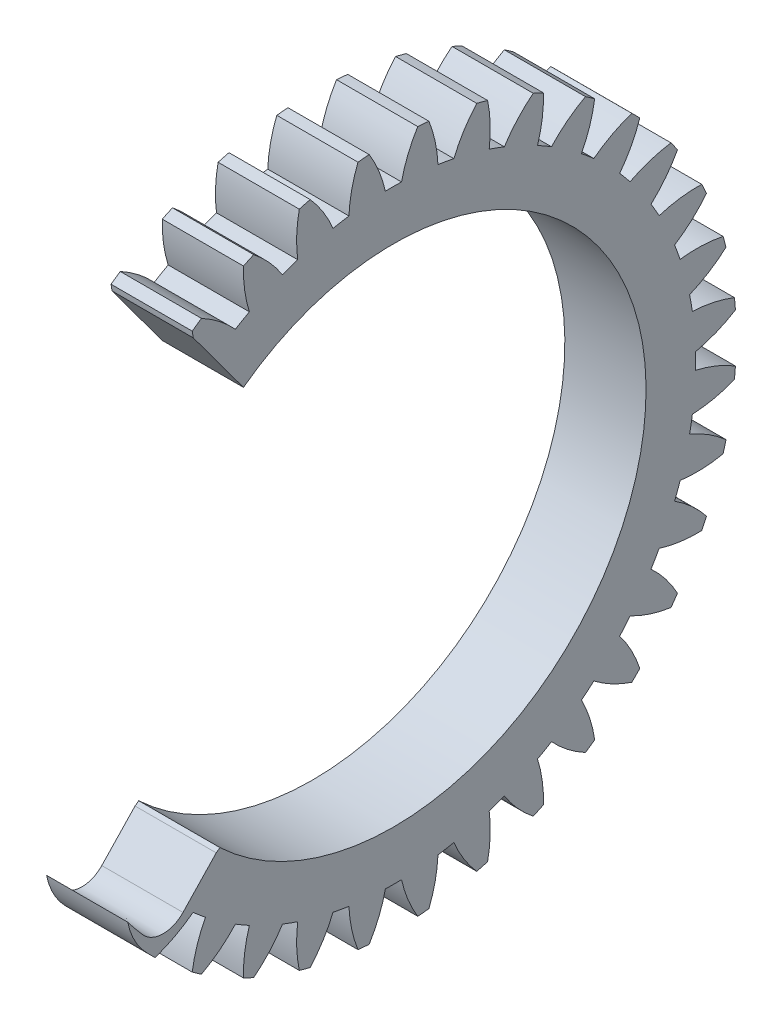
SolidWorks part; units mm, degrees
ref_plane "Plane1" through (0, 0, 0) normal (0, 0, 1) x (1, 0, 0)
ref_plane "Plane2" through (0, 0, 0) normal (0, 1, 0) x (1, 0, 0)
ref_plane "Plane3" through (0, 0, 0) normal (1, 0, 0) x (0, 0, -1)
sketch "HoldingSke" plane through (0, 0, 0) normal (0, 1, 0) x (1, 0, 0)
  line L0 (0, 0) -> (0.4045, -0.2939)
  line L1 (-15, 0) -> (100, 0) construction
  line L2 (0, 0) -> (-2.1039, 2.3779)
  line L3 (0, 0) -> (-11.863, 4.5341)
  line L4 (0, 0) -> (6.9867, 5.0761)
  line L5 (0, 0) -> (-46.8476, -17.4728)
  line L6 (0, 0) -> (-7.4607, -5.0337)
  line L7 (-2.1039, 2.3779) -> (8.6586, 51.2059)
  line L8 (-76.2, 54.61) -> (-71.9, 54.61)
  line L9 (-71.009, 38.7566) -> (-53.1078, 45.2721)
  line L10 (-76.2, 71.12) -> (104.1128, 71.12)
  line L11 (0, 0) -> (-9, 0)
  line L12 (-76.2, 101.6) -> (-76.133, 101.6)
  line L13 (24.9733, 27.94) -> (52.9518, 28.4284)
  line L14 (24.9733, 27.94) -> (24.9743, 27.94)
  line L15 (24.9733, 27.94) -> (100.4006, 29.5858)
  line L16 (-63.627, -2) -> (-12.827, -2)
  circle A0 centre (0, 0) radius 28
  circle A1 centre (0, 0) radius 33.499
  circle A2 centre (0, 0) radius 37.5
  circle A3 centre (0, 0) radius 28
  dimension "Num_teeth" = 36
  dimension "Pitch_radius" = 180.3128
  dimension "Width" = 9
  dimension "Thickness" = 9
sketch "BasProSke" plane through (0, 0, 0) normal (0, 1, 0) x (1, 0, 0)
  line L0 (-10, 0) -> (60, 0) construction
  line L1 (0, 0) -> (0, 38)
  line L2 (0, 0) -> (9, 0)
  line L3 (9, 0) -> (9, 38)
  line L4 (9, 38) -> (0, 38)
  dimension "Thickness" = 9
  dimension "Diameter" = 76
revolve "Base-Revolve" add sketch "BasProSke" angle 360 about L0
sketch "TooCutSke" plane through (0, 0, 0) normal (1, 0, 0) x (0, 0, -1)
  line L1 (0, 0) -> (0, 107) construction
  line L2 (0, 0) -> (-1.6875, 35.9604) construction
  line L3 (0, 0) -> (-6.2701, 71.6676) construction
  line L4 (-1.6875, 35.9604) -> (-3.135, 35.8338) construction
  arc A0 (0.8949, 33.487) -> (-0.8949, 33.487) centre (0, 0) ccw
  arc A1 (2.7061, 37.929) -> (-2.7061, 37.929) centre (0, 0) ccw
  circle A2 centre (0, 0) radius 36 construction
  circle A3 centre (0, 0) radius 33.8289 construction
  arc A4 (-0.8949, 33.487) -> (-2.7061, 37.929) centre (-14.9484, 30.347) ccw
  arc A5 (2.7061, 37.929) -> (0.8949, 33.487) centre (14.9484, 30.347) ccw
extrude "ToothCut" cut sketch "TooCutSke" along normal through all
fillet "Breaks" [suppressed] radius 0.04 tangent propagation no
fillet "RootFillets" [suppressed] radius 0.501
pattern_circular "TeethCuts" count 36 every 10 about axis through (-10, 0, 0) along (1, 0, 0) of "ToothCut", "RootFillets", "Breaks"
sketch "HubNeaOneSke" plane through (0, 0, 0) normal (-1, 0, 0) x (0, 0, 1)
  circle A0 centre (0, 0) radius 33.499
  dimension "Diameter" = 66.998
extrude "HubNearOne" [suppressed] add sketch "HubNeaOneSke" along normal blind 41.0001
sketch "HubNeaBotSke" plane through (0, 0, 0) normal (-1, 0, 0) x (0, 0, 1)
  circle A0 centre (0, 0) radius 33.499
  dimension "Diameter" = 66.998
extrude "HubNearBoth" [suppressed] add sketch "HubNeaBotSke" along normal blind 20.5
ref_plane "FarPln" through (9, 0, 0) normal (1, 0, 0) x (0, 0, -1)
sketch "HubFarSke" plane through (9, 0, 0) normal (1, 0, 0) x (0, 0, -1)
  circle A0 centre (0, 0) radius 33.499
  dimension "Diameter" = 66.998
extrude "HubFar" [suppressed] add sketch "HubFarSke" along normal blind 20.5
sketch "BorSke" plane through (0, 0, 0) normal (1, 0, 0) x (0, 0, -1)
  circle A0 centre (0, 0) radius 28
  dimension "Diameter" = 56
extrude "Bore" cut sketch "BorSke" along normal mid plane 100.0001
sketch "KeySke" plane through (0, 0, 0) normal (1, 0, 0) x (0, 0, -1)
  line L0 (-8, 0) -> (-8, 32.3)
  line L1 (-8, 32.3) -> (8, 32.3)
  line L2 (8, 32.3) -> (8, 0)
  line L3 (0, 0) -> (0, 34) construction
  line L4 (-8, 0) -> (8, 0)
  dimension "Width" = 16
extrude "Keyway" [suppressed] cut sketch "KeySke" along normal mid plane 100.0001
pattern_circular "Keyway2" [suppressed] count 2 every 90 about axis through (-10, 0, 0) along (1, 0, 0) reverse direction yes
sketch "Szkic1" plane through (0, 0, 0) normal (1, 0, 0) x (0, 0, -1)
  line L0 (0, 0) -> (-27.328, 37.0259)
  line L1 (-27.328, 37.0259) -> (-47.6164, -10.233)
  line L2 (-47.6164, -10.233) -> (0, 0)
extrude "Wytnij-wyciągnięcie1" cut sketch "Szkic1" along normal through all
sketch "Szkic2" plane through (0, 0, 0) normal (1, 0, 0) x (0, 0, -1)
  line L0 (-19.6433, -20.6493) -> (-23.3286, -24.5233) construction
  line L1 (-19.6433, -20.6493) -> (-23.3286, -24.5233)
  line L2 (-24.5118, 27.7159) -> (-14.2182, -16.6493)
  line L3 (-14.2182, -16.6493) -> (-19.6433, -20.6493)
  line L4 (-24.5118, 27.7159) -> (-50.9594, 25.255)
  line L5 (-50.9594, 25.255) -> (-37.7356, -29.3697)
  line L6 (-37.7356, -29.3697) -> (-27.7664, -24.4546)
  line L7 (-26.426, -27.3069) -> (-27.3069, -26.426)
  line L8 (-26.426, -27.3069) -> (-25.0675, -25.4318)
  arc A0 (-24.5118, 27.7159) -> (-27.7664, -24.4546) centre (0, 0) ccw construction
  arc A1 (-24.5118, 27.7159) -> (-27.7664, -24.4546) centre (0, 0) ccw
  arc A2 (-27.3069, -26.426) -> (-29.4473, -22.4022) centre (-21.7924, -20.9115) cw
  spline S0 degree 3 poles (273874.4752, 339512.8811) (7601.5471, 9915.3257) (-154.6056, 69.8177) (-27.1426, -24.9996) (-26.9606, -25.1074) (-26.5829, -25.2806) (-26.3868, -25.3469) (-25.9801, -25.4387) (-25.7711, -25.4633) (-25.3572, -25.469) (-25.1483, -25.4503) (-24.7384, -25.37) (-24.5404, -25.3094) (-24.158, -25.1482) (-23.9725, -25.0463) (116.7418, 72.2858) (-8418.6296, 11508.4077) (-264794.1332, 346856.9186) knots -95.625864 -95.625864 -95.625864 -95.625864 0.125 0.125 0.25 0.25 0.375 0.375 0.5 0.5 0.625 0.625 0.75 0.75 0.875 0.875 103.797727 103.797727 103.797727 103.797727 only from (-27.7664, -24.4546) to (-23.3286, -24.5233) construction
  spline S1 degree 3 poles (-27.7664, -24.4546) (-27.6277, -24.6121) (-27.4749, -24.7523) (-27.1426, -24.9996) (-26.9606, -25.1074) (-26.5829, -25.2806) (-26.3868, -25.3469) (-25.9801, -25.4387) (-25.7711, -25.4633) (-25.3572, -25.469) (-25.1483, -25.4503) (-24.7384, -25.37) (-24.5404, -25.3094) (-24.158, -25.1482) (-23.9725, -25.0463) (-23.6312, -24.8102) (-23.4733, -24.6754) (-23.3286, -24.5233) knots 0 0 0 0 0.125 0.125 0.25 0.25 0.375 0.375 0.5 0.5 0.625 0.625 0.75 0.75 0.875 0.875 1 1 1 1
extrude "Wytnij-wyciągnięcie2" cut sketch "Szkic2" against normal blind 43 and the other way through all contours A1 L4 L5 L6 | A1 S1 L1 L3 L2 region at (0, -1.5762, 26.5296) region at (0, 4.8425, 39.1923)
extrude "Dodanie-wyciągnięcie1" add sketch "Szkic2<3>" along normal up to surface (9 mm away) contours A2 L6 A1 | S1 L6 A2 L7 L8 region at (0, -25.7946, 26.8655) region at (0, -23.8723, 28.649) up to face at (9, -1.2954, -9.9994)
sketch "Szkic2<3>" plane through (0, 0, 0) normal (1, 0, 0) x (0, 0, -1) same geometry as "Szkic2"
equation "' \"Module@HoldingSke\" = 6.35"
equation "' \"Num_teeth@HoldingSke\" = 12"
equation "' \"Ap@HoldingSke\" =  20"
equation "' \"Ap@HoldingSke\" = 20"
equation "' \"Width@HoldingSke\" = 0.5 * 25.4"
equation "' \"Hub_dia@HoldingSke\"= 1 * 25.4"
equation "' \"Hub_dia@HoldingSke\" = 1 * 25.4"
equation "' \"Overall_len@HoldingSke\" = 1.0 * 25.4"
equation "' \"Bore@HoldingSke\" = 0.75 * 25.4"
equation "' \"T_dim@HoldingSke\" = 0.1 * 25.4"
equation "' \"Width@KeySke\" = 0.25 * 25.4"
equation "' \"Show_teeth@HoldingSke\" = 13"
equation "' \"Backlash@HoldingSke\" = 0.009 * 25.4"
equation "' \"Addendum_fac@HoldingSke\" = 1.0"
equation "' \"Dedendum_fac@HoldingSke\" = 1.25"
equation "' \"Dedendum_add@HoldingSke\" = 0.00005 * 25.4"
equation "' \"Clearance_fac@HoldingSke\" = 0.25"
equation "\"Pitch@HoldingSke\" = 1 / \"Module@HoldingSke\""
equation "\"Overcut_dia@TooCutSke\" = (\"Num_teeth@HoldingSke\" + 2 * \"Addendum_fac@HoldingSke\") / \"Pitch@HoldingSke\" + 0.002 * 25.4"
equation "\"Pitch_dia@TooCutSke\" = \"Num_teeth@HoldingSke\" / \"Pitch@HoldingSke\""
equation "\"Base_dia@TooCutSke\" = \"Num_teeth@HoldingSke\" / \"Pitch@HoldingSke\" * cos((\"Ap@HoldingSke\"  * 3.14159265 / 180))"
equation "\"Root_dia@TooCutSke\" = (\"Num_teeth@HoldingSke\" + 2) / \"Pitch@HoldingSke\" - 2 * (\"Addendum_fac@HoldingSke\" + \"Dedendum_fac@HoldingSke\") / \"Pitch@HoldingSke\" - \"Dedendum_add@HoldingSke\" * 2"
equation "\"Half_ang@TooCutSke\" = 180 / \"Num_teeth@HoldingSke\""
equation "\"Half_CT@TooCutSke\" = \"Num_teeth@HoldingSke\" / \"Pitch@HoldingSke\" * sin((3.14159265 / 2 / \"Num_teeth@HoldingSke\")) / 2 - 7 * \"Backlash@HoldingSke\" / 4"
equation "\"Flank_rad@TooCutSke\" = \"Num_teeth@HoldingSke\" / \"Pitch@HoldingSke\" / 5"
equation "\"Radius@RootFillets\" = \"Clearance_fac@HoldingSke\" / \"Pitch@HoldingSke\" + \"Dedendum_add@HoldingSke\""
equation "\"Break_rad@Breaks\" = 0.02 / \"Pitch@HoldingSke\""
equation "\"Thickness@HoldingSke\" = \"Width@HoldingSke\""
equation "\"OAL@HoldingSke\" = \"Thickness@HoldingSke\""
equation "\"MHD@HoldingSke\" = (\"Num_teeth@HoldingSke\" + 2) / \"Pitch@HoldingSke\" - 2 * (\"Addendum_fac@HoldingSke\" + \"Dedendum_fac@HoldingSke\")  / \"Pitch@HoldingSke\" - \"Dedendum_add@HoldingSke\" * 2"
equation "\"MBD@HoldingSke\" = (\"Num_teeth@HoldingSke\" + 2) / \"Pitch@HoldingSke\" - 2 * (\"Addendum_fac@HoldingSke\" + \"Dedendum_fac@HoldingSke\")  / \"Pitch@HoldingSke\" - \"Dedendum_add@HoldingSke\" * 2 - 0.002 * 25.4"
equation "\"MHD@HoldingSke\" = ((sgn( \"MHD@HoldingSke\" - \"Hub_dia@HoldingSke\" )-1)*( \"MHD@HoldingSke\" - \"Hub_dia@HoldingSke\" ))/-2+ \"Hub_dia@HoldingSke\""
equation "\"MBD@HoldingSke\" = ((sgn( \"MBD@HoldingSke\" - \"Bore@HoldingSke\" )-1)*( \"MBD@HoldingSke\" - \"Bore@HoldingSke\" ))/-2+ \"Bore@HoldingSke\""
equation "\"OAL@HoldingSke\" = ((sgn( \"OAL@HoldingSke\" - \"Overall_len@HoldingSke\" )+1)*( \"OAL@HoldingSke\" - \"Overall_len@HoldingSke\" ))/2 + \"Overall_len@HoldingSke\" + 0.000002 * 25.4"
equation "\"Num_teeth@TeethCuts\" = int( \"Show_teeth@HoldingSke\" ) + 1"
equation "\"Num_teeth@TeethCuts\" = ((sgn( \"Num_teeth@TeethCuts\" - \"Num_teeth@HoldingSke\" )-1)*( \"Num_teeth@TeethCuts\" - \"Num_teeth@HoldingSke\" ))/-2+ \"Num_teeth@HoldingSke\""
equation "\"Num_teeth@TeethCuts\" = ((sgn( \"Num_teeth@TeethCuts\" - 2.0)+1)*( \"Num_teeth@TeethCuts\" - 2.0))/2 +2.0"
equation "\"Angle@TeethCuts\" = 360.0 / \"Num_teeth@HoldingSke\""
equation "\"Diameter@BasProSke\" = (\"Num_teeth@HoldingSke\" + 2 * \"Addendum_fac@HoldingSke\") / \"Pitch@HoldingSke\""
equation "\"Thickness@BasProSke\"  = \"Thickness@HoldingSke\""
equation "' \"Fillet_rad@BasProSke\" =  \"Thickness@HoldingSke\" * 0.05"
equation "' \"Fillet_rad@BasProSke\" = \"Thickness@HoldingSke\" * 0.05"
equation "\"MHD@HoldingSke\" = ((sgn( \"MHD@HoldingSke\" - \"Root_dia@TooCutSke\" )-1)*( \"MHD@HoldingSke\" - \"Root_dia@TooCutSke\" ))/-2+ \"Root_dia@TooCutSke\""
equation "\"Diameter@HubNeaOneSke\" = \"MHD@HoldingSke\""
equation "\"Length@HubNearOne\" = \"OAL@HoldingSke\" - \"Thickness@BasProSke\""
equation "\"Diameter@HubNeaBotSke\" = \"MHD@HoldingSke\""
equation "\"Length@HubNearBoth\" = ( \"OAL@HoldingSke\" - \"Thickness@BasProSke\" ) / 2.0"
equation "\"Thickness@FarPln\" = \"Thickness@BasProSke\""
equation "\"Diameter@HubFarSke\" = \"MHD@HoldingSke\""
equation "\"Length@HubFar\" = ( \"OAL@HoldingSke\" - \"Thickness@BasProSke\" ) / 2.0"
equation "\"Diameter@BorSke\" = \"MBD@HoldingSke\""
equation "\"D1@Bore\" = \"OAL@HoldingSke\" * 2.0"
equation "\"D1@Keyway\" = \"OAL@HoldingSke\" * 2.0"
equation "\"Offset@KeySke\" = \"T_dim@HoldingSke\" + \"MBD@HoldingSke\" / 2.0"
